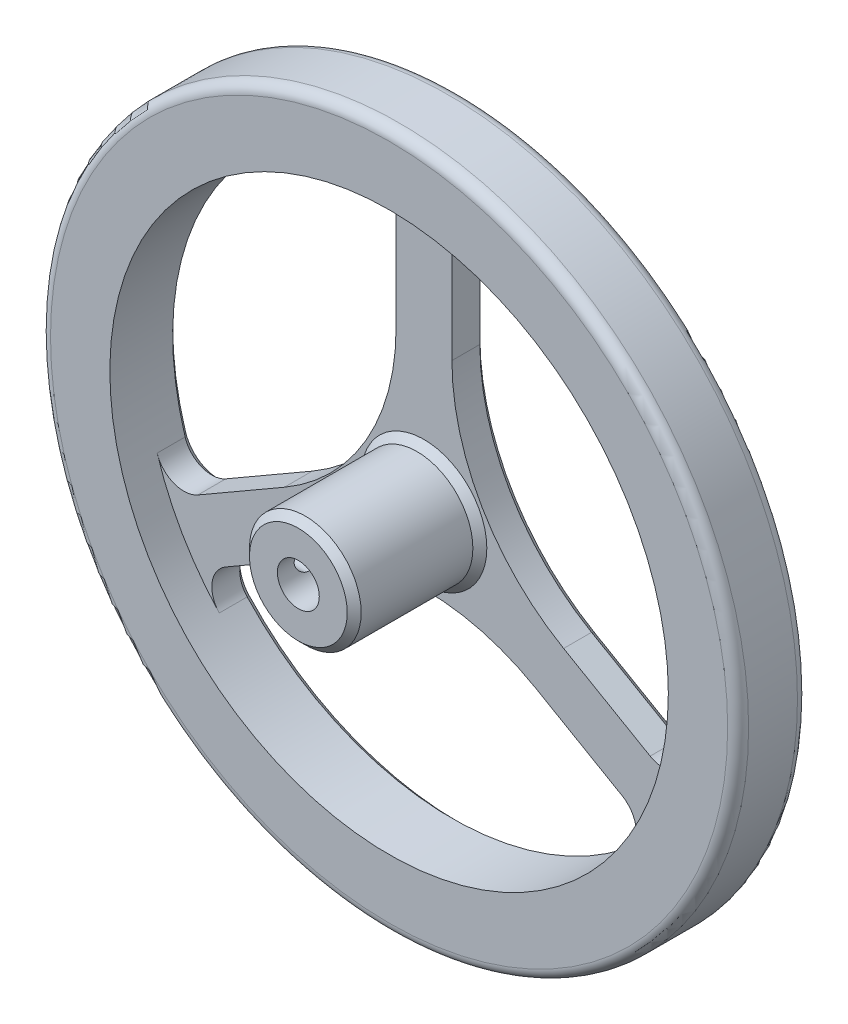
SolidWorks part; units mm, degrees
material "1060 Alloy"
ref_plane "Front" through (0, 0, 0) normal (0, 0, 1) x (1, 0, 0)
ref_plane "Top" through (0, 0, 0) normal (0, 1, 0) x (1, 0, 0)
ref_plane "Right" through (0, 0, 0) normal (1, 0, 0) x (0, 0, -1)
sketch "Sketch1" plane through (0, 0, 0) normal (0, 0, 1) x (1, 0, 0)
  line L0 (-4, 39.7995) -> (-4, -6.9282)
  line L1 (4, 39.7995) -> (4, -6.9282)
  line L2 (36.4674, -16.4356) -> (-4, 6.9282)
  line L3 (32.4674, -23.3639) -> (-8, 0)
  line L4 (-32.4674, -23.3639) -> (8, 0)
  line L5 (-36.4674, -16.4356) -> (4, 6.9282)
  circle A0 centre (0, 0) radius 50
  circle A1 centre (0, 0) radius 40
  circle A2 centre (0, 0) radius 8
  dimension "D1" = 50
  dimension "D5" = 8
  dimension "D3" = 8
  dimension "D4" = 4
  dimension "D2" = 10
  dimension "D6" = 3
extrude "Boss-Extrude1" add sketch "Sketch1" along normal blind 10 contours A0 A1 region at (-48.5858, 0, 0)
extrude "Boss-Extrude3" add sketch "Sketch1<5>" along normal blind 5 contours L3 A2 L2 L4 L1 | A2 L3 A1 L2 | L1 A2 L0 L2 L5 | A2 L5 A1 L4 | L5 A2 L4 L0 L3 | A2 L1 A1 L0 | L0 L5 L2 | L5 L2 L1 | L5 L3 L0 | L0 L4 L3 | L1 L4 L2 | L4 L3 L1 | L5 L0 L3 L4 L1 L2 region at (0, 23.7916, 0) region at (-2.6667, 4.6188, 0) region at (0, 6.6215, 0) region at (-20.6041, -11.8958, 0) region at (0, 0, 0) region at (-5.3333, 0, 0) region at (2.6667, 4.6188, 0) region at (-5.7344, -3.3108, 0) region at (-2.6667, -4.6188, 0) region at (5.3333, 0, 0) region at (5.7344, -3.3108, 0) region at (20.6041, -11.8958, 0) region at (2.6667, -4.6188, 0)
sketch "Sketch1<5>" plane through (0, 0, 0) normal (0, 0, 1) x (1, 0, 0) same geometry as "Sketch1"
fillet "Fillet1" radius 32 3 edges at (0, -4.6188, 2.5) (-4, 2.3094, 2.5) (4, 2.3094, 2.5)
fillet "Fillet2" radius 4 6 edges at (36.4674, -16.4356, 2.5) (32.4674, -23.3639, 2.5) (-36.4674, -16.4356, 2.5) (-32.4674, -23.3639, 2.5) (-4, 39.7995, 2.5) (4, 39.7995, 2.5)
chamfer "Chamfer1" distance 1 angle 45 18 edges at (5.5056, 38.2268, 0) (8.2872, 4.7846, 0) (35.8582, -14.3454, 0) (34.641, 20, 0) (0, -9.5692, 0) (-30.3526, -23.8814, 0) (30.3526, -23.8814, 0) (0, -40, 0) (-8.2872, 4.7846, 0) (-5.5056, 38.2268, 0) (-35.8582, -14.3454, 0) (-34.641, 20, 0) (-4, 27.9422, 0) (-26.1987, -10.507, 0) (-22.1987, -17.4352, 0) (22.1987, -17.4352, 0) (26.1987, -10.507, 0) (4, 27.9422, 0)
fillet "Fillet3" radius 1.5 2 edges at (50, 0, 10) (50, 0, 0)
sketch "Sketch2" plane through (0, 0, 5) normal (0, 0, 1) x (1, 0, 0)
  circle A0 centre (0, 0) radius 8
  circle A2 centre (0, 0) radius 3
  dimension "D1" = 8
  dimension "D2" = 6
extrude "Boss-Extrude4" add sketch "Sketch2" along normal blind 18
chamfer "Chamfer2" distance 1 angle 45 2 edges at (8, 0, 23) (8, 0, 5)
sketch "Sketch3" plane through (0, 0, 0) normal (1, 0, 0) x (0, 0, -1)
  line L0 (-5, 20.7846) -> (-5, -6.9282) construction
  circle A0 centre (-19, 0) radius 1.6
  circle A1 centre (-13, 0) radius 1.6
  point P0 (-13, 0)
  point P1 (-19, 0)
  dimension "D3" = 3.2
  dimension "D1" = 8
  dimension "D2" = 6
extrude "Cut-Extrude1" cut sketch "Sketch3" against normal blind 10
equation "\"R\"= 50mm'Wheel Radius"
equation "\"T\"= 10mm'Wheel thickness"
equation "\"IT\"= 8mm'Stroke thickness"
equation "\"D1@Sketch1\"=\"R\""
equation "\"D2@Sketch1\"=\"R\"*0.2"
equation "\"D3@Sketch1\"=\"IT\""
equation "\"D4@Sketch1\"=\"IT\"/2"
equation "\"IR\"= 8mm'internal radius"
equation "\"D5@Sketch1\"=\"IR\""
equation "\"D1@Boss-Extrude1\"=\"T\""
equation "\"D1\"= \"T\" * 0.5"
equation "\"D1@Fillet1\"=\"IR\"*4"
equation "\"D1@Fillet2\"=\"IR\"*0.5"
equation "\"C\"= 1mm'Chamfer and  fillet"
equation "\"D1@Chamfer1\"=\"C\""
equation "\"D1@Fillet3\"=\"C\"*1.5"
equation "\"SR\"= 8mm'Shaft mount radius"
equation "\"D1@Sketch2\"=\"SR\""
